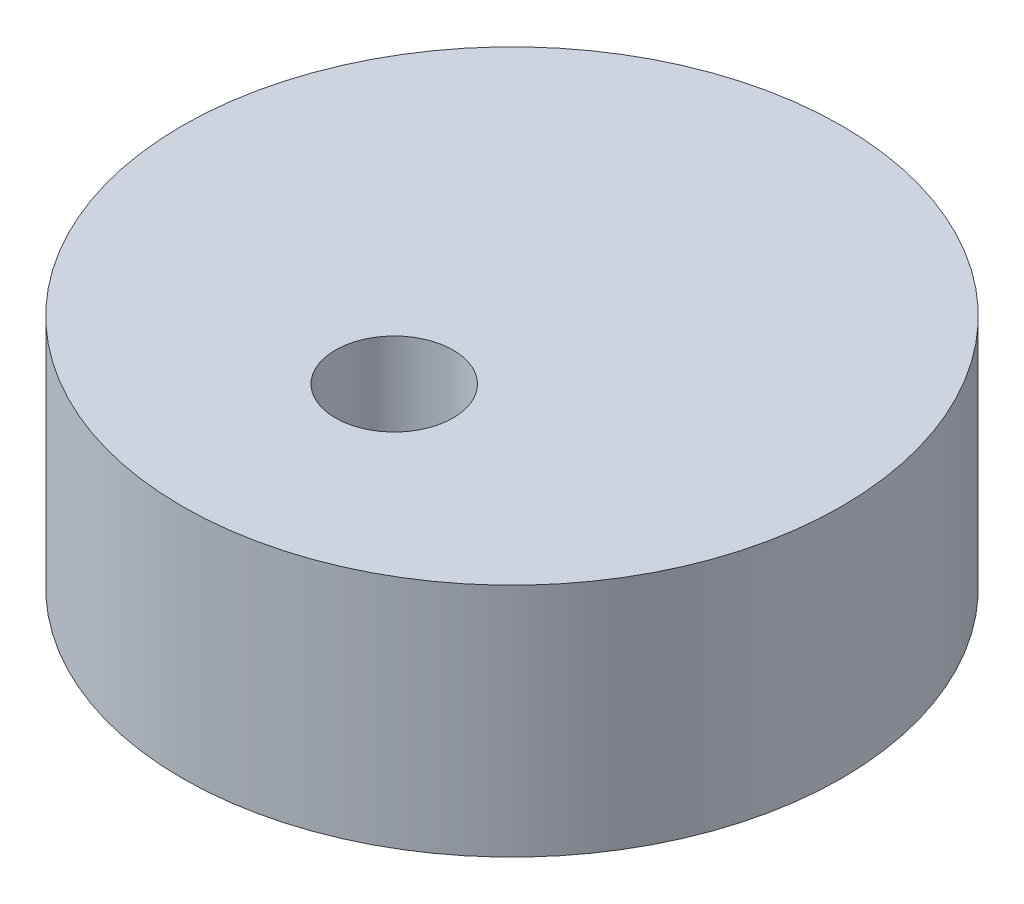
SolidWorks part; units mm, degrees
ref_plane "Front Plane" through (0, 0, 0) normal (0, 0, 1) x (1, 0, 0)
ref_plane "Top Plane" through (0, 0, 0) normal (0, 1, 0) x (1, 0, 0)
ref_plane "Right Plane" through (0, 0, 0) normal (1, 0, 0) x (0, 0, -1)
sketch "Sketch1" plane through (0, 0, 0) normal (0, 1, 0) x (1, 0, 0)
  line L0 (0, -3.175) -> (0, 0) construction
  circle A0 centre (0, 0) radius 8.89
  circle A1 centre (0, -3.175) radius 1.5875
  dimension "D1" = 17.78
  dimension "D2" = 3.175
  dimension "D3" = 3.175
extrude "Boss-Extrude1" add sketch "Sketch1" along normal blind 6.35
equation "\"R\"= 1.5in'radius of rotor"
equation "\"E\"= .125in'eccentricity"
equation "\"R_r\"= .25in'radius of roller"
equation "\"N\"= 8'number of rollers"
equation "\"R_o\"= .125in'output disk pin diameter"
equation "\"D3@Sketch1\"=\"E\""
